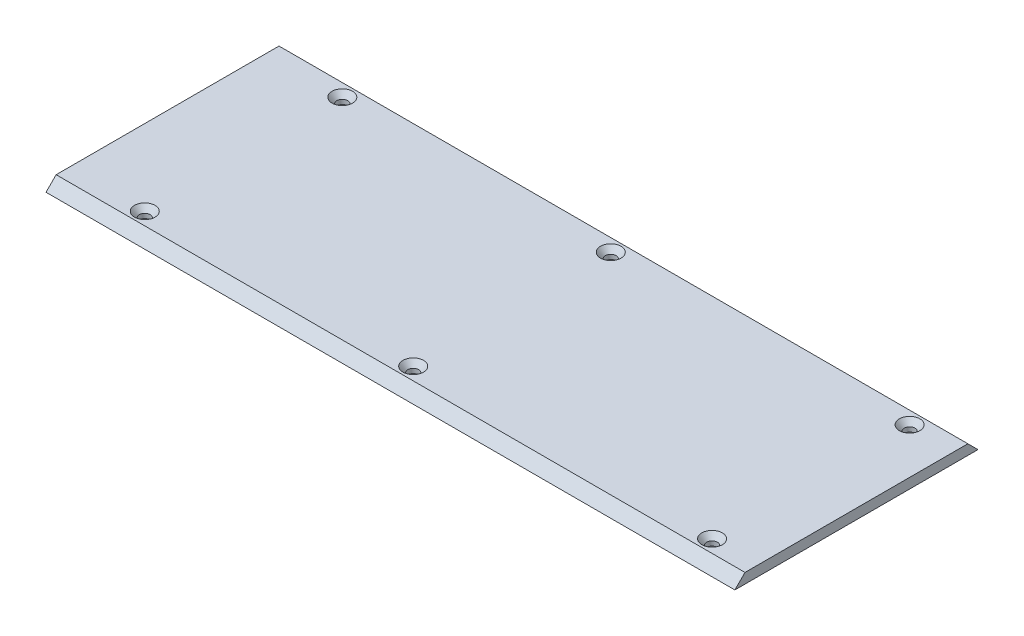
SolidWorks part; units mm, degrees
material "PE High Density"
ref_plane "Front Plane" through (0, 0, 0) normal (0, 0, 1) x (1, 0, 0)
ref_plane "Top Plane" through (0, 0, 0) normal (0, 1, 0) x (1, 0, 0)
ref_plane "Right Plane" through (0, 0, 0) normal (1, 0, 0) x (0, 0, -1)
sketch "Sketch1" plane through (0, 0, 0) normal (0, 1, 0) x (1, 0, 0)
  line L1 (-215.9, -76.2) -> (215.9, -76.2)
  line L2 (-215.9, -76.2) -> (-215.9, 76.2)
  line L3 (-215.9, 76.2) -> (215.9, 76.2)
  line L4 (215.9, -76.2) -> (215.9, 76.2)
  line L5 (-215.9, -76.2) -> (215.9, 76.2) construction
  line L6 (-215.9, 76.2) -> (215.9, -76.2) construction
  point P0 (0, 0)
  dimension "D1" = 431.8
  dimension "D2" = 152.4
extrude "Boss-Extrude1" add sketch "Sketch1" along normal blind 6.35
chamfer "Chamfer1" distance 6.35 angle 45 2 edges at (0, 6.35, 76.2) (0, 6.35, -76.2)
hole_wizard "CSK for 1/4 Flat Head Machine Screw1" positions "Sketch2" profile "Sketch3" countersink size "1/4" standard "ANSI Inch" end condition through all
sketch "Sketch2" plane through (0, 6.35, 0) normal (0, 1, 0) x (1, 0, 0)
  line L1 (215.9, -69.85) -> (215.9, 69.85) construction
  line L2 (-215.9, 0) -> (215.9, 0) construction
  line L3 (-215.9, 69.85) -> (-215.9, -69.85) construction
  line L5 (215.9, -61.9125) -> (-215.9, -61.9125) construction
  line L7 (-215.9, -76.2) -> (215.9, -76.2) construction
  point P0 (187.325, -61.9125)
  point P2 (0, -61.9125)
  point P4 (-168.275, -61.9125)
  point P22 (-168.275, 61.9125)
  point P23 (187.325, 61.9125)
  point P24 (0, 61.9125)
  dimension "D1" = 14.2875
  dimension "D2" = 28.575
  dimension "D3" = 215.9
  dimension "D4" = 384.175
sketch "Sketch3" plane through (187.325, 6.35, 61.9125) normal (1, 0, 0) x (0, 0, 1)
  line L0 (0, 0) -> (0, 6.35)
  line L1 (0, 6.35) -> (3.3782, 6.35)
  line L2 (3.3782, 6.35) -> (3.3782, 3.5209)
  line L3 (3.3782, 3.5209) -> (6.4389, 0)
  line L5 (6.4389, 0) -> (0, 0)
  line L6 (-3.3782, 3.5209) -> (-6.4389, 0) construction
  line L11 (0, -6.35) -> (0, 107.95) construction
  dimension "Thru Hole Dia." = 6.7564
  dimension "Thru Hole Depth" = 6.35
  dimension "Near C'Sink Dia." = 12.8778
  dimension "Near C'Sink Angle" = 82
